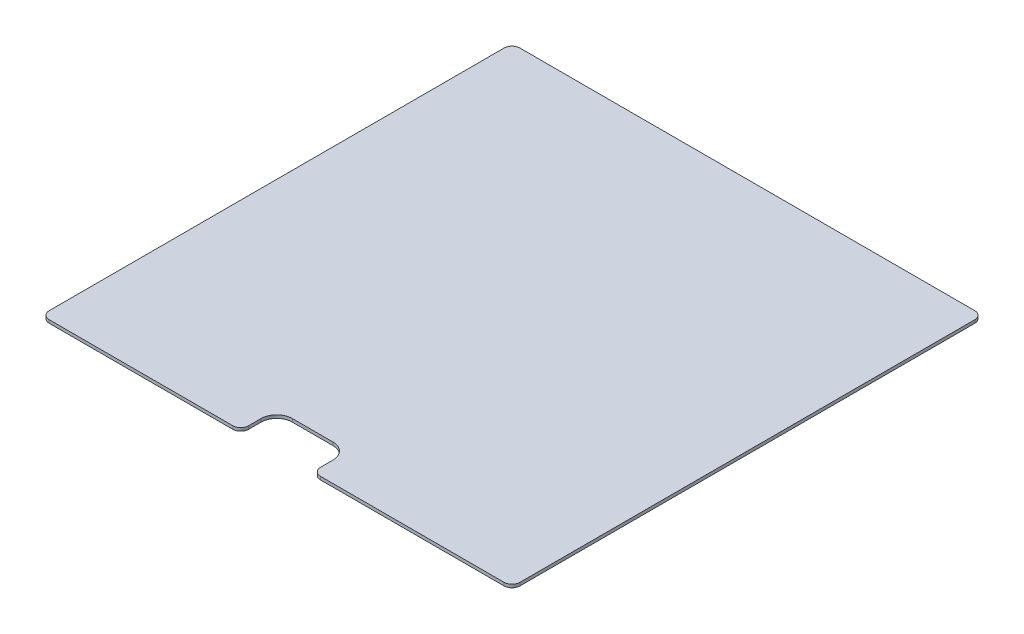
SolidWorks part; units mm, degrees
ref_plane "Front Plane" through (0, 0, 0) normal (0, 0, 1) x (1, 0, 0)
ref_plane "Top Plane" through (0, 0, 0) normal (0, 1, 0) x (1, 0, 0)
ref_plane "Right Plane" through (0, 0, 0) normal (1, 0, 0) x (0, 0, -1)
sketch "Sketch1" plane through (0, 0, 0) normal (0, 1, 0) x (1, 0, 0)
  line L0 (2.2929, -14.5) -> (2.2929, -13.7071)
  line L1 (14.5, -15) -> (2.7929, -15)
  line L2 (15, -14.5) -> (15, 14.5)
  line L3 (14.5, 15) -> (-14.5, 15)
  line L4 (-15, -14.5) -> (-15, 14.5)
  line L5 (15, -15) -> (-15, 15) construction
  line L6 (15, 15) -> (-15, -15) construction
  line L7 (1.2929, -12.7071) -> (-1.2929, -12.7071)
  line L8 (-2.2929, -13.7071) -> (-2.2929, -14.5)
  line L9 (-2.7929, -15) -> (-14.5, -15)
  arc A0 (-14.5, 15) -> (-15, 14.5) centre (-14.5, 14.5) ccw
  arc A1 (15, 14.5) -> (14.5, 15) centre (14.5, 14.5) ccw
  arc A2 (-14.5, -15) -> (-15, -14.5) centre (-14.5, -14.5) cw
  arc A3 (14.5, -15) -> (15, -14.5) centre (14.5, -14.5) ccw
  arc A4 (-2.2929, -14.5) -> (-2.7929, -15) centre (-2.7929, -14.5) cw
  arc A5 (2.2929, -14.5) -> (2.7929, -15) centre (2.7929, -14.5) ccw
  arc A6 (-1.2929, -12.7071) -> (-2.2929, -13.7071) centre (-1.2929, -13.7071) ccw
  arc A7 (2.2929, -13.7071) -> (1.2929, -12.7071) centre (1.2929, -13.7071) ccw
  point P0 (0, 0)
  point P9 (0, -12.7071)
  point P30 (0, 0)
  dimension "D2" = 0.5
  dimension "D3" = 0.5
  dimension "D4" = 1
  dimension "D1" = 30
extrude "Boss-Extrude1" add sketch "Sketch1" along normal mid plane 0.2
